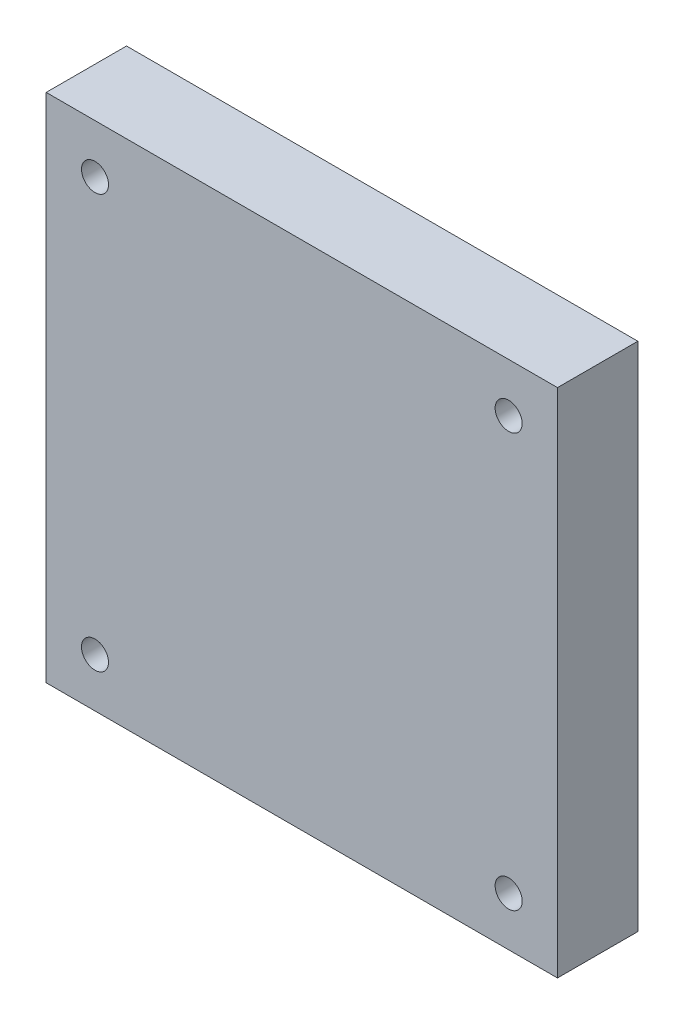
SolidWorks part; units mm, degrees
ref_plane "Top Plane" through (0, 0, 0) normal (0, 0, 1) x (1, 0, 0)
ref_plane "Right Plane" through (0, 0, 0) normal (0, 1, 0) x (1, 0, 0)
ref_plane "Front Plane" through (0, 0, 0) normal (1, 0, 0) x (0, 0, -1)
sketch "Sketch1" plane through (0, 0, 0) normal (0, 0, 1) x (1, 0, 0)
  line L1 (-25, -25) -> (25, -25)
  line L2 (-25, -25) -> (-25, 25)
  line L3 (-25, 25) -> (25, 25)
  line L4 (25, -25) -> (25, 25)
  line L5 (-25, -25) -> (25, 25) construction
  line L6 (-25, 25) -> (25, -25) construction
  point P0 (0, 0)
  dimension "D1" = 50
extrude "Boss-Extrude1" add sketch "Sketch1" along normal blind 1.4
sketch "Sketch2" plane through (0, 0, 1.4) normal (0, 0, 1) x (1, 0, 0)
  line L0 (-25, -20) -> (25, -20) construction
  line L1 (-25, 25) -> (-25, -25) construction
  line L2 (25, -25) -> (25, 25) construction
  line L3 (-25, -25) -> (25, -25) construction
  text T0 "A" font "Kozuka Gothic Pr6N M" height 40
  dimension "D1" = 5
extrude "a" [suppressed] add sketch "Sketch2" along normal blind 10 from surface
sketch "Sketch4" [suppressed] plane through (0, 0, 1.4) normal (0, 0, 1) x (1, 0, 0)
  line L0 (-25, -20) -> (25, -20) construction
  line L1 (-25, 25) -> (-25, -25) construction
  line L2 (25, -25) -> (25, 25) construction
  line L5 (-25, -25) -> (25, -25) construction
  text T0 "B" font "Kozuka Gothic Pr6N M" height 40
  dimension "D1" = 5
extrude "b" [suppressed] add sketch "Sketch4" along normal blind 10 from surface
sketch "Sketch6" plane through (0, 0, 1.4) normal (0, 0, 1) x (1, 0, 0)
  line L0 (-25, -20) -> (25, -20) construction
  line L1 (-25, 25) -> (-25, -25) construction
  line L2 (25, -25) -> (25, 25) construction
  line L3 (-25, -25) -> (25, -25) construction
  text T0 "C" font "Kozuka Gothic Pr6N M" height 40
  dimension "D1" = 5
extrude "c" [suppressed] add sketch "Sketch6" along normal blind 10 from surface
sketch "Sketch12" plane through (0, 0, 0) normal (0, 0, 1) x (1, 0, 0)
  line L0 (-25, -20) -> (25, -20) construction
  text T0 "D\r\n" font "Kozuka Gothic Pr6N M" height 40
extrude "d" add sketch "Sketch12" along normal blind 10
sketch "Sketch13" plane through (0, 0, 0) normal (0, 0, 1) x (1, 0, 0)
  line L0 (-25, -20) -> (25, -20) construction
  text T0 "E\r\n" font "Kozuka Gothic Pr6N M" height 40
extrude "e" [suppressed] add sketch "Sketch13" along normal blind 10
sketch "Sketch14" plane through (0, 0, 0) normal (0, 0, 1) x (1, 0, 0)
  line L0 (-25, -20) -> (25, -20) construction
  text T0 "F" font "Kozuka Gothic Pr6N M" height 40
extrude "f" [suppressed] add sketch "Sketch14" along normal blind 10
sketch "Sketch15" plane through (0, 0, 0) normal (0, 0, 1) x (1, 0, 0)
  line L0 (-25, -20) -> (25, -20) construction
  text T0 "H" font "Kozuka Gothic Pr6N M" height 40
extrude "h" [suppressed] add sketch "Sketch15" along normal blind 10
sketch "Sketch16" plane through (0, 0, 0) normal (0, 0, 1) x (1, 0, 0)
  line L0 (-25, -20) -> (25, -20) construction
  text T0 "I" font "Kozuka Gothic Pr6N M" height 40
extrude "i" [suppressed] add sketch "Sketch16" along normal blind 10
sketch "Sketch17" plane through (0, 0, 0) normal (0, 0, 1) x (1, 0, 0)
  line L0 (-25, -20) -> (25, -20) construction
  text T0 "O" font "Kozuka Gothic Pr6N M" height 40
extrude "o" [suppressed] add sketch "Sketch17" along normal blind 10
sketch "Sketch18" plane through (0, 0, 0) normal (0, 0, 1) x (1, 0, 0)
  line L0 (-25, -20) -> (25, -20) construction
  text T0 "P\r\n" font "Kozuka Gothic Pr6N M" height 40
extrude "p" [suppressed] add sketch "Sketch18" along normal blind 10
sketch "Sketch19" plane through (0, 0, 0) normal (0, 0, 1) x (1, 0, 0)
  line L0 (-25, -20) -> (25, -20) construction
  text T0 "Q" font "Kozuka Gothic Pr6N M" height 40
extrude "q" [suppressed] add sketch "Sketch19" along normal blind 10
sketch "Sketch20" plane through (0, 0, 0) normal (0, 0, 1) x (1, 0, 0)
  line L0 (-25, -20) -> (25, -20) construction
  text T0 "T" font "Kozuka Gothic Pr6N M" height 40
extrude "t" [suppressed] add sketch "Sketch20" along normal blind 10
sketch "Sketch21" plane through (0, 0, 0) normal (0, 0, 1) x (1, 0, 0)
  line L0 (-25, -20) -> (25, -20) construction
  text T0 "U" font "Kozuka Gothic Pr6N M" height 40
extrude "u" [suppressed] add sketch "Sketch21" along normal blind 10
sketch "Sketch23" [suppressed] plane through (0, 0, 0) normal (0, 0, 1) x (1, 0, 0)
  line L0 (-9, 18) -> (-25, 18) construction
  line L2 (-25, 25) -> (-25, -25) construction
  line L3 (25, 25) -> (-25, 25) construction
  text T0 "<b><r90>子</r></b>" font "@Microsoft YaHei" height 27
  dimension "D1" = 16
  dimension "D2" = 7
extrude "zi" [suppressed] add sketch "Sketch23" along normal blind 10
sketch "Sketch24" [suppressed] plane through (0, 0, 0) normal (0, 0, 1) x (1, 0, 0)
  line L0 (-9, 18) -> (-25, 18) construction
  text T0 "<b><r90>孑</r></b>" font "@Microsoft YaHei" height 27
  dimension "D1" = 16
extrude "jie" [suppressed] add sketch "Sketch24" along normal blind 10
sketch "Sketch25" [suppressed] plane through (0, 0, 0) normal (0, 0, 1) x (1, 0, 0)
  line L0 (-9, 18) -> (-25, 18) construction
  text T0 "<b><r90>孓</r></b>" font "@Microsoft YaHei" height 27
  dimension "D1" = 16
extrude "jue" [suppressed] add sketch "Sketch25" along normal blind 10
sketch "Sketch5" plane through (0, -25, 0) normal (0, -1, 0) x (1, 0, 0)
  line L0 (-25, 1.4) -> (25, 1.4) construction
  line L1 (-19.5, 1.4) -> (19.5, 1.4) construction
  line L2 (-19.5, 1.4) -> (-19.5, 10) construction
  line L3 (-19.5, 10) -> (19.5, 10)
  line L4 (19.5, 1.4) -> (19.5, 10) construction
  line L5 (0, 1.4) -> (0, 0) construction
  line L6 (-25, 0) -> (25, 0) construction
  arc A0 (-19.5, 10) -> (19.5, 10) centre (0, 45.525) ccw
  point P11 (0, 5)
  dimension "D1" = 39
  dimension "D3" = 5
  dimension "D2" = 10
extrude "1-concave" [suppressed] cut sketch "Sketch5" against normal through all
sketch "Sketch7" [suppressed] plane through (0, -25, 0) normal (0, -1, 0) x (1, 0, 0)
  line L1 (-19, 1.4) -> (19, 1.4) construction
  line L2 (-19, 1.4) -> (-19, 10)
  line L3 (-19, 10) -> (19, 10)
  line L4 (19, 1.4) -> (19, 10)
  line L5 (-25, 1.4) -> (25, 1.4) construction
  line L6 (0, 10) -> (0, 0) construction
  line L8 (-25, 0) -> (25, 0) construction
  arc A0 (-19, 1.4) -> (19, 1.4) centre (0, -15.8881) cw
  point P4 (0, 9.8)
  point P18 (0, 1.4)
  dimension "D2" = 10
  dimension "D3" = 38
  dimension "D1" = 0.2
extrude "2-convexe" [suppressed] cut sketch "Sketch7" against normal through all
sketch "Sketch8" plane through (0, -25, 0) normal (0, -1, 0) x (1, 0, 0)
  line L0 (-25, 1.4) -> (25, 1.4) construction
  line L1 (-19, 1.4) -> (19, 1.4) construction
  line L2 (-19, 1.4) -> (-19, 10)
  line L4 (19, 1.4) -> (19, 10)
  line L5 (0, 1.4) -> (0, 0) construction
  line L6 (-25, 0) -> (25, 0) construction
  line L7 (-12.6667, 10) -> (-12.6667, 7.7) construction
  line L8 (-19, 10) -> (-12.6667, 10)
  line L9 (-6.3333, 5) -> (-6.3333, 10) construction
  line L10 (-12.6667, 10) -> (-6.3333, 10)
  line L11 (0, 7.9) -> (0, 10) construction
  line L12 (-6.3333, 10) -> (0, 10)
  line L13 (6.3333, 6) -> (6.3333, 10) construction
  line L14 (0, 10) -> (6.3333, 10)
  line L15 (12.6667, 8.2) -> (12.6667, 10) construction
  line L16 (6.3333, 10) -> (12.6667, 10)
  line L17 (12.6667, 10) -> (19, 10)
  spline S0 degree 3 poles (-19, 1.4) (-19, 9.6976) (-13.012, 8.8687) (-6.3294, 2.8817) (-0.2093, 10.0435) (6.4447, 4.2742) (13.3036, 9.5469) (19, 9.0457) (19, 1.4) knots 0 0 0 0 0.196796 0.348468 0.501921 0.647587 0.795287 1 1 1 1
  dimension "D1" = 10
  dimension "D2" = 38
  dimension "D3" = 2.3
  dimension "D4" = 5
  dimension "D5" = 2.1
  dimension "D6" = 4
  dimension "D7" = 1.8
extrude "3-wave" [suppressed] cut sketch "Sketch8" against normal through all
sketch "Sketch32" plane through (0, -25, 0) normal (0, -1, 0) x (1, 0, 0)
  line L0 (0, 9.99) -> (0, 0) construction
  line L1 (25, 9.99) -> (-25, 9.99)
  line L2 (25, 9.99) -> (25, 14.99)
  line L3 (25, 14.99) -> (-25, 14.99)
  line L4 (-25, 9.99) -> (-25, 14.99)
  line L5 (-25, 0) -> (25, 0) construction
  line L6 (25, 1.4) -> (25, 0) construction
  line L9 (25, 0) -> (-25, 0) construction
  dimension "D2" = 5
  dimension "D1" = 9.99
extrude "4-flat" cut sketch "Sketch32" against normal through all
sketch "Sketch9" plane through (0, 0, 1.4) normal (0, 0, 1) x (1, 0, 0)
  line L0 (-25, 25) -> (-28.3137, 28.3137) construction
  line L1 (-35, -35) -> (35, -35)
  line L2 (-35, -35) -> (-35, 35)
  line L3 (-35, 35) -> (35, 35)
  line L4 (35, -35) -> (35, 35)
  line L5 (-35, -35) -> (35, 35) construction
  line L6 (-35, 35) -> (35, -35) construction
  line L7 (-28.3137, -28.3137) -> (28.3137, -28.3137) construction
  line L8 (-28.3137, -28.3137) -> (-28.3137, 28.3137) construction
  line L9 (-28.3137, 28.3137) -> (28.3137, 28.3137) construction
  line L10 (28.3137, -28.3137) -> (28.3137, 28.3137) construction
  line L11 (-28.3137, -28.3137) -> (28.3137, 28.3137) construction
  line L12 (-28.3137, 28.3137) -> (28.3137, -28.3137) construction
  line L14 (-28.3137, 28.3137) -> (-33, 28.3137) construction
  line L15 (25, -25) -> (-25, -25) construction
  line L16 (25, -25) -> (25, 25) construction
  line L17 (25, 25) -> (-25, 25) construction
  line L18 (-25, -25) -> (-25, 25) construction
  line L19 (25, -25) -> (-25, 25) construction
  line L20 (25, 25) -> (-25, -25) construction
  line L21 (-33, 28.3137) -> (-33, 33) construction
  line L22 (-33, 33) -> (-28.3137, 33) construction
  line L23 (-28.3137, 33) -> (-28.3137, 28.3137) construction
  circle A0 centre (28.3137, -28.3137) radius 1.85
  circle A1 centre (-28.3137, -28.3137) radius 1.85
  circle A2 centre (-28.3137, 28.3137) radius 1.85
  circle A3 centre (28.3137, 28.3137) radius 1.85
  point P0 (0, 0)
  point P14 (0, 0)
  point P16 (0, 0)
  dimension "D2" = 3.7
  dimension "D1" = 70
  dimension "D3" = 50
  dimension "D4" = 2
extrude "Boss-Extrude5" add sketch "Sketch9" along normal blind 10 separate body
combine bodies "Combine1" operation type subtract main body 110 bodies to subtract 159
sketch "Sketch11" plane through (0, 0, 1.4) normal (0, 0, -1) x (-1, 0, 0)
  line L1 (-25, -25) -> (25, -25)
  line L2 (-25, -25) -> (-25, 25)
  line L3 (-25, 25) -> (25, 25)
  line L4 (-35, 35) -> (-35, -35)
  line L5 (-35, -35) -> (35, -35)
  line L6 (35, -35) -> (35, 35)
  line L7 (35, 35) -> (-35, 35)
  line L8 (-35, 35) -> (-35, -35)
  line L9 (-35, -35) -> (35, -35)
  line L10 (35, -35) -> (35, 35)
  line L11 (35, 35) -> (-35, 35)
  line L12 (25, -25) -> (25, 25)
  line L13 (-25, -25) -> (25, 25) construction
  line L14 (-25, 25) -> (25, -25) construction
  circle A0 centre (-28.3137, -28.3137) radius 1.85 construction
  circle A1 centre (28.3137, -28.3137) radius 1.85 construction
  circle A2 centre (28.3137, 28.3137) radius 1.85 construction
  circle A3 centre (-28.3137, 28.3137) radius 1.85 construction
  circle A4 centre (-28.3137, -28.3137) radius 1.85
  circle A5 centre (28.3137, -28.3137) radius 1.85
  circle A6 centre (28.3137, 28.3137) radius 1.85
  circle A7 centre (-28.3137, 28.3137) radius 1.85
  point P16 (0, 0)
  dimension "D2" = 50
  dimension "D1" = 0
extrude "Boss-Extrude7" add sketch "Sketch11" along normal blind 1
sketch "Sketch26" plane through (0, -35, 0) normal (0, -1, 0) x (1, 0, 0)
  line L0 (35, 9.9) -> (-35, 9.9) construction
  line L1 (35, 11.4) -> (35, 0.4) construction
  line L2 (-35, 11.4) -> (-35, 0.4) construction
  text T0 "<b>3-wave</b>" font "Century Gothic" height 7.5
  dimension "D1" = 1.5
extrude "text-3" [suppressed] cut sketch "Sketch26" against normal blind 1
sketch "Sketch30" [suppressed] plane through (0, -35, 0) normal (0, -1, 0) x (1, 0, 0)
  line L0 (35, 9.9) -> (-35, 9.9) construction
  line L3 (35, 11.4) -> (35, 0.4) construction
  line L4 (-35, 11.4) -> (-35, 0.4) construction
  line L5 (-35, 11.4) -> (35, 11.4) construction
  text T0 "<b>2-convex</b>" font "Century Gothic" height 7.5
  dimension "D1" = 1.5
sketch "Sketch31" [suppressed] plane through (0, -35, 0) normal (0, -1, 0) x (1, 0, 0)
  line L0 (35, 9.9) -> (-35, 9.9) construction
  line L3 (35, 11.4) -> (35, 0.4) construction
  line L4 (-35, 11.4) -> (-35, 0.4) construction
  line L5 (-35, 11.4) -> (35, 11.4) construction
  text T0 "<b>1-convave</b>" font "Century Gothic" height 7.5
  dimension "D1" = 1.5
extrude "text-2" [suppressed] cut sketch "Sketch30" against normal blind 1
extrude "text-1" [suppressed] cut sketch "Sketch31" against normal blind 1
sketch "Sketch33" plane through (0, -35, 0) normal (0, -1, 0) x (1, 0, 0)
  line L0 (35, 9.9) -> (-35, 9.9) construction
  line L3 (-35, 11.4) -> (-35, 0.4) construction
  line L4 (35, 11.4) -> (35, 0.4) construction
  line L5 (-35, 11.4) -> (35, 11.4) construction
  text T0 "<b>4-flat</b>" font "Century Gothic" height 7.5
  dimension "D1" = 1.5
extrude "text-4" cut sketch "Sketch33" against normal blind 1
sketch "Sketch34" [suppressed] plane through (0, 0, 1.4) normal (0, 0, 1) x (1, 0, 0)
  line L4 (-35, -35) -> (35, -35)
  line L5 (35, -35) -> (35, 35)
  line L6 (35, 35) -> (-35, 35)
  line L7 (-35, 35) -> (-35, -35)
  line L8 (-35, -35) -> (35, -35)
  line L9 (35, -35) -> (35, 35)
  line L10 (35, 35) -> (-35, 35)
  line L11 (-35, 35) -> (-35, -35)
  circle A0 centre (28.3137, 28.3137) radius 2.35
  circle A1 centre (28.3137, 28.3137) radius 1.85
  circle A2 centre (28.3137, 28.3137) radius 1.85 construction
  circle A3 centre (-28.3137, 28.3137) radius 1.85
  circle A4 centre (-28.3137, 28.3137) radius 1.85 construction
  circle A5 centre (-28.3137, -28.3137) radius 1.85
  circle A6 centre (-28.3137, -28.3137) radius 1.85 construction
  circle A7 centre (28.3137, -28.3137) radius 1.85
  circle A8 centre (28.3137, -28.3137) radius 1.85 construction
  circle A9 centre (28.3137, -28.3137) radius 2.35
  circle A10 centre (-28.3137, -28.3137) radius 2.35
  circle A11 centre (-28.3137, 28.3137) radius 2.35
  dimension "D1" = 0
  dimension "D2" = 0
  dimension "D3" = 0
  dimension "D4" = 0
  dimension "D5" = 0
  dimension "D6" = 0.5
extrude "hard" [suppressed] add sketch "Sketch34" against normal blind 4
equation "\"D1@a\"=\"h\""
equation "\"h\"= 10"
equation "\"D1@c\"=\"h\""
equation "\"D1@b\"=\"h\""
equation "\"D1@d\"=\"h\""
equation "\"D1@e\"=\"h\""
equation "\"D1@f\"=\"h\""
equation "\"D1@h\"=\"h\""
equation "\"D1@i\"=\"h\""
equation "\"D1@o\"=\"h\""
equation "\"D1@p\"=\"h\""
equation "\"D1@q\"=\"h\""
equation "\"D1@t\"=\"h\""
equation "\"D1@u\"=\"h\""
equation "\"D1@Boss-Extrude5\"=\"h\""
equation "\"D2@Sketch5\"=\"h\""
equation "\"D2@Sketch7\"=\"h\""
equation "\"D1@Sketch8\"=\"h\""
equation "\"D1@zi\" = \"h\""
equation "\"D1@jie\" = \"h\""
equation "\"D1@jue\" = \"h\""
equation "\"D1@Sketch32\"=\"h\"-0.01"
